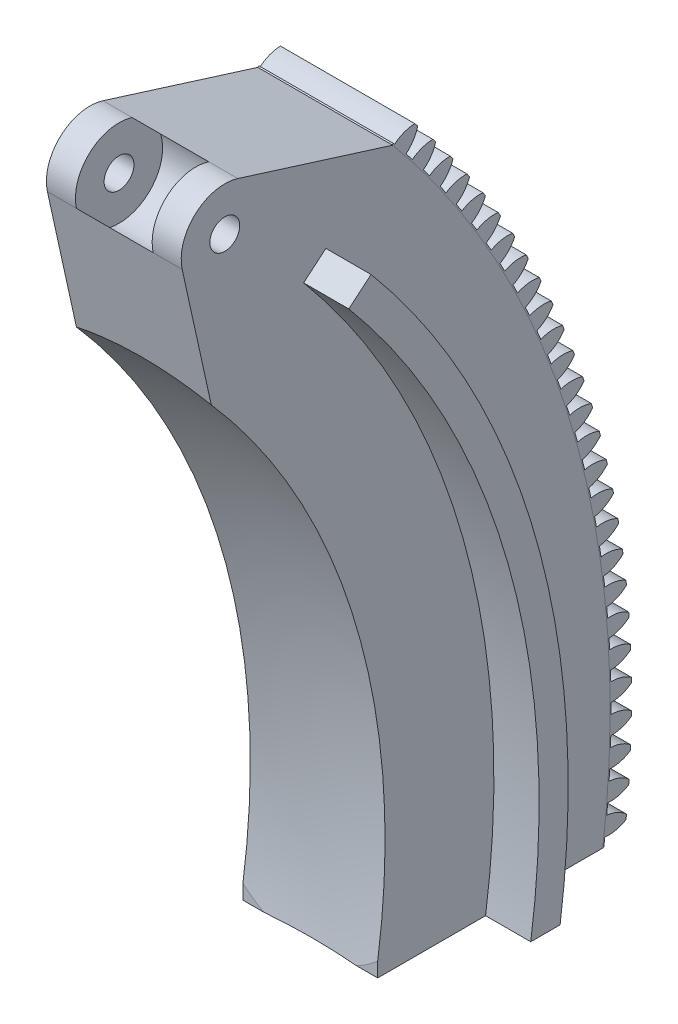
SolidWorks part; units mm, degrees
material "ABS"
ref_plane "Front Plane" through (0, 0, 0) normal (0, 0, 1) x (1, 0, 0)
ref_plane "Top Plane" through (0, 0, 0) normal (0, 1, 0) x (1, 0, 0)
ref_plane "Right Plane" through (0, 0, 0) normal (1, 0, 0) x (0, 0, -1)
ref_plane "Plane2" through (6.35, 0, 0) normal (1, 0, 0) x (0, 0, -1)
sketch "Sketch1" plane through (0, 0, 0) normal (1, 0, 0) x (0, 0, -1)
  line L0 (-1000, 0) -> (152.4, 0) construction
  line L1 (152.4, 0) -> (152.4, -25.4)
  line L2 (0, 0) -> (116.7452, 97.9608) construction
  line L4 (203.2, 0) -> (49000, 0) construction
  line L7 (152.4, -25.4) -> (203.2, -25.4) construction
  line L8 (203.2, 0) -> (203.2, -25.4) construction
  line L10 (-19.9245, -15.6845) -> (159.6649, 125.6875) construction
  line L61 (160.8976, 124.1056) -> (0, 0) construction
  line L62 (116.7452, 97.9608) -> (109.6694, 130.0821)
  line L64 (152.4, -25.4) -> (201.6062, -25.4)
  line L65 (116.7452, 97.9608) -> (136.2027, 114.2876) construction
  line L66 (136.2027, 114.2876) -> (155.6602, 130.6144) construction
  line L68 (0, 0) -> (35966.99, 34732.9185) construction
  line L69 (159.6736, 125.6943) -> (159.6985, 125.714) construction
  line L70 (0, 0) -> (118.9714, 132.1311) construction
  line L71 (121.82, 141.2202) -> (155.6602, 130.6144)
  arc A2 (152.4, 0) -> (116.7452, 97.9608) centre (0, 0) ccw
  circle A19 centre (0, 0) radius 203.2 construction
  arc A22 (155.6602, 130.6144) -> (203.2, 0) centre (0, 0) cw
  arc A23 (203.2, 0) -> (201.6062, -25.4) centre (0, 0) cw
  arc A24 (109.6694, 130.0821) -> (121.82, 141.2202) centre (118.9714, 132.1311) cw
  point P6 (159.6985, 125.714)
  point P7 (116.7452, 97.9608)
  dimension "D1" = 152.4
  dimension "D2" = 6.35
  dimension "D12" = 406.4
  dimension "D8" = 9.525
  dimension "D3" = 40
  dimension "D4" = 50.8
  dimension "D5" = 25.4
  dimension "D6" = 177.8
  dimension "D7" = 48
  dimension "D13" = 44
sketch "Sketch2" plane through (6.35, 0, 0) normal (1, 0, 0) x (0, 0, -1)
  line L0 (0, 0) -> (165.1, 0) construction
  line L1 (165.1, 0) -> (190.5, 0) construction
  line L2 (0, 0) -> (49240.3877, 8682.4089) construction
  circle A0 centre (165.1, 0) radius 3.2639
  circle A1 centre (190.5, 0) radius 3.2639
  arc A3 (165.1, 0) -> (162.5918, 28.6693) centre (0, 0) ccw construction
  circle A4 centre (162.5918, 28.6693) radius 3.2639
  arc A5 (190.5, 0) -> (187.6059, 33.08) centre (0, 0) ccw construction
  circle A6 centre (187.6059, 33.08) radius 3.2639
  dimension "D3" = 6.5278
  dimension "D4" = 6.5278
  dimension "D6" = 6.5278
  dimension "D7" = 6.5278
  dimension "D1" = 165.1
  dimension "D2" = 25.4
  dimension "D5" = 10
sketch "Sketch11" plane through (6.35, 0, 0) normal (1, 0, 0) x (0, 0, -1)
  line L0 (-785.502, -659.1144) -> (0, 0) construction
  line L2 (-1000, 0) -> (0, 0) construction
  line L4 (155.6602, 130.6144) -> (159.3372, 133.6998)
  line L5 (159.3372, 133.6998) -> (921.7047, 773.4021) construction
  line L6 (208, 0) -> (208, -25.4) construction
  line L7 (208, -25.4) -> (198.9391, -25.4) construction
  line L8 (201.6062, -25.4) -> (206.4433, -25.4)
  line L9 (203.2, 0) -> (208, 0) construction
  arc A0 (-230, 0) -> (-176.1902, -147.8412) centre (0, 0) ccw construction
  arc A1 (-208, 0) -> (-159.3372, -133.6998) centre (0, 0) ccw construction
  arc A2 (-205.6, 0) -> (-157.4987, -132.1571) centre (0, 0) ccw construction
  arc A3 (208, 0) -> (159.3372, 133.6998) centre (0, 0) ccw
  arc A4 (230, 0) -> (176.1902, 147.8412) centre (0, 0) ccw construction
  arc A5 (-205.6, 0) -> (-157.4987, -132.1571) centre (0, 0) ccw
  arc A6 (155.6602, 130.6144) -> (203.2, 0) centre (0, 0) cw
  arc A7 (208, 0) -> (206.4433, -25.4) centre (0, 0) cw
  arc A8 (203.2, 0) -> (201.6062, -25.4) centre (0, 0) cw
  dimension "D1" = 460
  dimension "D2" = 416
  dimension "D4" = 203.2
  dimension "D3" = 2.4
  dimension "D6" = 25.4
extrude "Boss-Extrude2" add sketch "Sketch11" against normal blind 6.35 contours A3 L4 region at (6.35, 130.8741, -158.5753)
sketch "Sketch12" plane through (6.35, 0, 0) normal (1, 0, 0) x (0, 0, -1)
  line L0 (0, 0) -> (208, 0) construction
  line L2 (205.994, 1.5708) -> (205.994, -1.5708) construction
  line L3 (0, 0) -> (203.4969, 1.1234) construction
  line L4 (201.6783, 0) -> (208.9831, 2.6587) construction
  line L5 (0, 0) -> (208.9757, 3.1872) construction
  line L6 (205.994, 1.5708) -> (205.9461, 4.712) construction
  circle A0 centre (0, 0) radius 206 construction
  arc A1 (206.4433, -25.4) -> (159.3372, 133.6998) centre (0, 0) ccw construction
  circle A2 centre (0, 0) radius 203.5 construction
  arc A3 (203.4969, 1.1234) -> (208.9694, 3.5771) centre (203.4559, 8.5441) ccw
  arc A4 (207.4358, -25.5221) -> (208.9694, -3.5771) centre (0, 0) cw construction
  arc A5 (203.4969, -1.1234) -> (208.9694, -3.5771) centre (203.4559, -8.5441) cw
  arc A6 (207.4358, -25.5221) -> (160.1033, 134.3426) centre (0, 0) ccw
  arc A7 (207.4358, -25.5221) -> (208.9694, 3.5771) centre (0, 0) ccw construction
  arc A8 (203.4969, 1.1234) -> (203.4969, -1.1234) centre (0, 0) cw
  arc A9 (206.4433, -25.4) -> (159.3372, 133.6998) centre (0, 0) ccw construction
  arc A10 (208.9694, 3.5771) -> (208.9694, -3.5771) centre (0, 0) cw
  dimension "D1" = 412
  dimension "D3" = 20
  dimension "D4" = 0.874
  dimension "D5" = 4.5
  dimension "D2" = 1
extrude "Boss-Extrude3" add sketch "Sketch1" along normal blind 29.464
extrude "Cut-Extrude4" cut sketch "Sketch12" against normal blind 6.35
pattern_circular "CirPattern3" count 206 every 1.748 about axis through (0, 0, 0) along (1, 0, 0) of "Cut-Extrude4"
sketch "Sketch15" plane through (6.35, 0, 0) normal (1, 0, 0) x (0, 0, -1)
  line L0 (0, 0) -> (118.9714, 132.1311) construction
  line L2 (0, 0) -> (102.4673, 0) construction
  circle A0 centre (118.9714, 132.1311) radius 3.2639
  dimension "D3" = 6.5278
  dimension "D1" = 177.8
  dimension "D2" = 48
extrude "Cut-Extrude7" cut sketch "Sketch15" against normal through all both and the other way through all
sketch "Sketch21" plane through (0, 0, 0) normal (0, 1, 0) x (1, 0, 0)
  line L0 (0, 0) -> (-11.1125, 0) construction
  line L1 (12.7, 0) -> (12.7, 152.4) construction
  line L2 (0, 0) -> (12.7, 0) construction
  line L3 (-11.1125, 0) -> (-11.1125, 38.1) construction
  line L4 (-11.1125, 38.1) -> (-127.8666, 38.1) construction
  line L5 (-11.1125, 38.1) -> (105.6416, 38.1) construction
  line L6 (107.5153, 38.1) -> (-49892.4847, 38.1) construction
  line L7 (-1000, 0) -> (49000, 0) construction
  line L8 (14.732, 38.1) -> (14.732, 152.4) construction
  line L9 (29.464, 152.4) -> (0, 152.4) construction
  line L10 (-76.1776, 38.1) -> (157.3306, 38.1) construction
  line L11 (29.464, 152.4) -> (0, 152.4) construction
  line L12 (0, 152.4) -> (14.732, 152.4) construction
  line L13 (14.732, 152.4) -> (14.732, 130.0627) construction
  line L15 (-76.1776, 38.1) -> (-102.108, 38.1)
  line L16 (105.6416, 38.1) -> (131.572, 38.1)
  line L17 (-76.1776, 38.1) -> (105.6416, 38.1)
  arc A0 (105.6416, 38.1) -> (-127.8666, 38.1) centre (-11.1125, 38.1) ccw construction
  arc A1 (-76.1776, 38.1) -> (157.3306, 38.1) centre (40.5765, 38.1) cw construction
  arc A2 (-102.108, 38.1) -> (131.572, 38.1) centre (14.732, 38.1) cw
  dimension "D3" = 12.7
  dimension "D5" = 116.84
  dimension "D1" = 11.1125
  dimension "D2" = 152.4
  dimension "D4" = 38.1
revolve "Cut-Revolve7" cut sketch "Sketch21" angle 360 about L7 reverse direction yes
sketch "Sketch22" plane through (6.35, 0, 0) normal (1, 0, 0) x (0, 0, -1)
  line L0 (0, 0) -> (118.9714, 132.1311)
  line L1 (0, 0) -> (177.8, 0)
  dimension "D1" = 177.8
sketch "Sketch23" plane through (0, 0, 0) normal (1, 0, 0) x (0, 0, -1)
  line L0 (0, 0) -> (152.4, 0) construction
  line L1 (0, 0) -> (116.7452, 97.9608) construction
  line L2 (152.4, 0) -> (171.45, 0) construction
  line L3 (116.7452, 97.9608) -> (136.2027, 114.2876) construction
  line L5 (136.2027, 114.2876) -> (141.0671, 118.3693)
  line L7 (175.9764, -25.4) -> (0, 0) construction
  line L8 (182.3899, -25.4) -> (175.9764, -25.4)
  line L9 (152.4, -25.4) -> (201.9086, -25.4) construction
  arc A0 (152.4, 0) -> (116.7452, 97.9608) centre (0, 0) ccw construction
  circle A2 centre (171.45, 0) radius 6.35 construction
  arc A3 (177.8, 0) -> (136.2027, 114.2876) centre (0, 0) ccw
  arc A4 (184.15, 0) -> (141.0671, 118.3693) centre (0, 0) ccw
  circle A5 centre (190.5, 0) radius 6.35 construction
  arc A6 (177.8, 0) -> (175.9764, -25.4) centre (0, 0) cw
  arc A7 (184.15, 0) -> (182.3899, -25.4) centre (0, 0) cw
  dimension "D4" = 6.35
  dimension "D5" = 12.7
  dimension "D6" = 12.7
  dimension "D1" = 152.4
  dimension "D2" = 40
  dimension "D3" = 19.05
extrude "Boss-Extrude4" add sketch "Sketch23" against normal blind 9.8742
ref_plane "Plane3" through (14.732, 0, 0) normal (1, 0, 0) x (0, 0, -1)
mirror "Mirror2" about plane through (14.732, 0, 0) normal (1, 0, 0) of "Boss-Extrude4"
sketch "Sketch27" plane through (6.35, 0, 0) normal (1, 0, 0) x (0, 0, -1)
  line L2 (155.89, 130.8073) -> (155.6602, 130.6144)
  line L3 (201.6062, -25.4) -> (201.9086, -25.4)
  line L4 (155.89, 130.8073) -> (155.6602, 130.6144)
  line L6 (201.6062, -25.4) -> (201.9086, -25.4)
  arc A95 (207.805, 9.0055) -> (207.7585, 10.0204) centre (0, 0) ccw
  arc A111 (203.368, 7.3287) -> (207.805, 9.0055) centre (203.1007, 14.7447) ccw
  arc A112 (203.368, 7.3287) -> (207.805, 9.0055) centre (203.1007, 14.7447) ccw
  arc A113 (207.7585, 10.0204) -> (203.1869, 11.2847) centre (203.5984, 3.8753) ccw
  arc A114 (207.7585, 10.0204) -> (203.1869, 11.2847) centre (203.5984, 3.8753) ccw
  arc A115 (203.1869, 11.2847) -> (203.0499, 13.5273) centre (0, 0) ccw
  arc A116 (203.1869, 11.2847) -> (203.0499, 13.5273) centre (0, 0) ccw
  arc A117 (203.0499, 13.5273) -> (207.4337, 15.3385) centre (202.5566, 20.9317) ccw
  arc A118 (203.0499, 13.5273) -> (207.4337, 15.3385) centre (202.5566, 20.9317) ccw
  arc A119 (207.4337, 15.3385) -> (207.3563, 16.3516) centre (0, 0) ccw
  arc A120 (207.4337, 15.3385) -> (207.3563, 16.3516) centre (0, 0) ccw
  arc A121 (207.3563, 16.3516) -> (202.7482, 17.4759) centre (203.3855, 10.0825) ccw
  arc A122 (207.3563, 16.3516) -> (202.7482, 17.4759) centre (203.3855, 10.0825) ccw
  arc A123 (202.7482, 17.4759) -> (202.5429, 19.7132) centre (0, 0) ccw
  arc A124 (202.7482, 17.4759) -> (202.5429, 19.7132) centre (0, 0) ccw
  arc A125 (202.5429, 19.7132) -> (206.8694, 21.6573) centre (201.8241, 27.0991) ccw
  arc A126 (202.5429, 19.7132) -> (206.8694, 21.6573) centre (201.8241, 27.0991) ccw
  arc A127 (206.8694, 21.6573) -> (206.7612, 22.6675) centre (0, 0) ccw
  arc A128 (206.8694, 21.6573) -> (206.7612, 22.6675) centre (0, 0) ccw
  arc A129 (206.7612, 22.6675) -> (202.121, 23.6508) centre (202.9834, 16.2802) ccw
  arc A130 (206.7612, 22.6675) -> (202.121, 23.6508) centre (202.9834, 16.2802) ccw
  arc A131 (202.121, 23.6508) -> (201.8476, 25.8808) centre (0, 0) ccw
  arc A132 (202.121, 23.6508) -> (201.8476, 25.8808) centre (0, 0) ccw
  arc A133 (201.8476, 25.8808) -> (206.1127, 27.956) centre (200.9038, 33.2414) ccw
  arc A134 (201.8476, 25.8808) -> (206.1127, 27.956) centre (200.9038, 33.2414) ccw
  arc A135 (206.1127, 27.956) -> (205.9737, 28.9624) centre (0, 0) ccw
  arc A136 (206.1127, 27.956) -> (205.9737, 28.9624) centre (0, 0) ccw
  arc A137 (205.9737, 28.9624) -> (201.3057, 29.8037) centre (202.3925, 22.4629) ccw
  arc A138 (205.9737, 28.9624) -> (201.3057, 29.8037) centre (202.3925, 22.4629) ccw
  arc A139 (201.3057, 29.8037) -> (200.9644, 32.0244) centre (0, 0) ccw
  arc A140 (201.3057, 29.8037) -> (200.9644, 32.0244) centre (0, 0) ccw
  arc A141 (200.9644, 32.0244) -> (205.1643, 34.2286) centre (199.7966, 39.3527) ccw
  arc A142 (200.9644, 32.0244) -> (205.1643, 34.2286) centre (199.7966, 39.3527) ccw
  arc A143 (205.1643, 34.2286) -> (204.9947, 35.2304) centre (0, 0) ccw
  arc A144 (205.1643, 34.2286) -> (204.9947, 35.2304) centre (0, 0) ccw
  arc A145 (204.9947, 35.2304) -> (200.3032, 35.9289) centre (201.6134, 28.6246) ccw
  arc A146 (204.9947, 35.2304) -> (200.3032, 35.9289) centre (201.6134, 28.6246) ccw
  arc A147 (200.3032, 35.9289) -> (199.8943, 38.1381) centre (0, 0) ccw
  arc A148 (200.3032, 35.9289) -> (199.8943, 38.1381) centre (0, 0) ccw
  arc A149 (199.8943, 38.1381) -> (204.0251, 40.4694) centre (198.5036, 45.4275) ccw
  arc A150 (199.8943, 38.1381) -> (204.0251, 40.4694) centre (198.5036, 45.4275) ccw
  arc A151 (204.0251, 40.4694) -> (203.825, 41.4655) centre (0, 0) ccw
  arc A152 (204.0251, 40.4694) -> (203.825, 41.4655) centre (0, 0) ccw
  arc A153 (203.825, 41.4655) -> (199.1143, 42.0207) centre (200.6467, 34.7598) ccw
  arc A154 (203.825, 41.4655) -> (199.1143, 42.0207) centre (200.6467, 34.7598) ccw
  arc A155 (199.1143, 42.0207) -> (198.6383, 44.2164) centre (0, 0) ccw
  arc A156 (199.1143, 42.0207) -> (198.6383, 44.2164) centre (0, 0) ccw
  arc A157 (198.6383, 44.2164) -> (202.696, 46.6726) centre (197.0259, 51.4599) ccw
  arc A158 (198.6383, 44.2164) -> (202.696, 46.6726) centre (197.0259, 51.4599) ccw
  arc A159 (202.696, 46.6726) -> (202.4656, 47.6621) centre (0, 0) ccw
  arc A160 (202.696, 46.6726) -> (202.4656, 47.6621) centre (0, 0) ccw
  arc A161 (202.4656, 47.6621) -> (197.7402, 48.0734) centre (199.4933, 40.8625) ccw
  arc A162 (202.4656, 47.6621) -> (197.7402, 48.0734) centre (199.4933, 40.8625) ccw
  arc A163 (197.7402, 48.0734) -> (197.1975, 50.2535) centre (0, 0) ccw
  arc A164 (197.7402, 48.0734) -> (197.1975, 50.2535) centre (0, 0) ccw
  arc A165 (197.1975, 50.2535) -> (201.1784, 52.8323) centre (195.3649, 57.4445) ccw
  arc A166 (197.1975, 50.2535) -> (201.1784, 52.8323) centre (195.3649, 57.4445) ccw
  arc A167 (201.1784, 52.8323) -> (200.9179, 53.8144) centre (0, 0) ccw
  arc A168 (201.1784, 52.8323) -> (200.9179, 53.8144) centre (0, 0) ccw
  arc A169 (200.9179, 53.8144) -> (196.1822, 54.0813) centre (198.1544, 46.9273) ccw
  arc A170 (200.9179, 53.8144) -> (196.1822, 54.0813) centre (198.1544, 46.9273) ccw
  arc A171 (196.1822, 54.0813) -> (195.5732, 56.2439) centre (0, 0) ccw
  arc A172 (196.1822, 54.0813) -> (195.5732, 56.2439) centre (0, 0) ccw
  arc A173 (195.5732, 56.2439) -> (199.4736, 58.9429) centre (193.5222, 63.3757) ccw
  arc A174 (195.5732, 56.2439) -> (199.4736, 58.9429) centre (193.5222, 63.3757) ccw
  arc A175 (199.4736, 58.9429) -> (199.1834, 59.9166) centre (0, 0) ccw
  arc A176 (199.4736, 58.9429) -> (199.1834, 59.9166) centre (0, 0) ccw
  arc A177 (199.1834, 59.9166) -> (194.4417, 60.039) centre (196.6311, 52.9484) ccw
  arc A178 (199.1834, 59.9166) -> (194.4417, 60.039) centre (196.6311, 52.9484) ccw
  arc A179 (194.4417, 60.039) -> (193.767, 62.182) centre (0, 0) ccw
  arc A180 (194.4417, 60.039) -> (193.767, 62.182) centre (0, 0) ccw
  arc A181 (193.767, 62.182) -> (197.5833, 64.9987) centre (191.4995, 69.2479) ccw
  arc A182 (201.6062, -25.4) -> (155.6602, 130.6144) centre (0, 0) ccw
  arc A183 (193.767, 62.182) -> (197.5833, 64.9987) centre (191.4995, 69.2479) ccw
  arc A184 (197.5833, 64.9987) -> (197.2635, 65.963) centre (0, 0) ccw
  arc A185 (197.5833, 64.9987) -> (197.2635, 65.963) centre (0, 0) ccw
  arc A186 (197.2635, 65.963) -> (192.5203, 65.9408) centre (194.9249, 58.9203) ccw
  arc A187 (197.2635, 65.963) -> (192.5203, 65.9408) centre (194.9249, 58.9203) ccw
  arc A189 (207.805, 9.0055) -> (207.7585, 10.0204) centre (0, 0) ccw
  arc A276 (201.6062, -25.4) -> (155.6602, 130.6144) centre (0, 0) ccw
  arc A282 (192.5203, 65.9408) -> (191.7806, 68.0622) centre (0, 0) ccw
  arc A283 (192.5203, 65.9408) -> (191.7806, 68.0622) centre (0, 0) ccw
  arc A284 (191.7806, 68.0622) -> (195.5092, 70.994) centre (189.2986, 75.0557) ccw
  arc A285 (191.7806, 68.0622) -> (195.5092, 70.994) centre (189.2986, 75.0557) ccw
  arc A286 (195.5092, 70.994) -> (195.1601, 71.9481) centre (0, 0) ccw
  arc A287 (195.5092, 70.994) -> (195.1601, 71.9481) centre (0, 0) ccw
  arc A288 (195.1601, 71.9481) -> (190.4198, 71.7812) centre (193.0374, 64.8374) ccw
  arc A289 (195.1601, 71.9481) -> (190.4198, 71.7812) centre (193.0374, 64.8374) ccw
  arc A290 (190.4198, 71.7812) -> (189.6157, 73.8791) centre (0, 0) ccw
  arc A291 (190.4198, 71.7812) -> (189.6157, 73.8791) centre (0, 0) ccw
  arc A292 (189.6157, 73.8791) -> (193.2532, 76.9233) centre (186.9217, 80.7937) ccw
  arc A293 (189.6157, 73.8791) -> (193.2532, 76.9233) centre (186.9217, 80.7937) ccw
  arc A294 (193.2532, 76.9233) -> (192.8752, 77.8663) centre (0, 0) ccw
  arc A295 (193.2532, 76.9233) -> (192.8752, 77.8663) centre (0, 0) ccw
  arc A296 (192.8752, 77.8663) -> (188.1422, 77.5549) centre (190.9703, 70.6941) ccw
  arc A297 (192.8752, 77.8663) -> (188.1422, 77.5549) centre (190.9703, 70.6941) ccw
  arc A298 (188.1422, 77.5549) -> (187.2745, 79.6273) centre (0, 0) ccw
  arc A299 (188.1422, 77.5549) -> (187.2745, 79.6273) centre (0, 0) ccw
  arc A300 (187.2745, 79.6273) -> (190.8175, 82.781) centre (184.3708, 86.4565) ccw
  arc A301 (187.2745, 79.6273) -> (190.8175, 82.781) centre (184.3708, 86.4565) ccw
  arc A302 (190.8175, 82.781) -> (190.4109, 83.712) centre (0, 0) ccw
  arc A303 (190.8175, 82.781) -> (190.4109, 83.712) centre (0, 0) ccw
  arc A304 (190.4109, 83.712) -> (185.6896, 83.2565) centre (188.7256, 76.4851) ccw
  arc A305 (190.4109, 83.712) -> (185.6896, 83.2565) centre (188.7256, 76.4851) ccw
  arc A306 (185.6896, 83.2565) -> (184.7591, 85.3014) centre (0, 0) ccw
  arc A307 (185.6896, 83.2565) -> (184.7591, 85.3014) centre (0, 0) ccw
  arc A308 (184.7591, 85.3014) -> (188.2042, 88.5617) centre (181.6485, 92.0389) ccw
  arc A309 (184.7591, 85.3014) -> (188.2042, 88.5617) centre (181.6485, 92.0389) ccw
  arc A310 (188.2042, 88.5617) -> (187.7694, 89.4799) centre (0, 0) ccw
  arc A311 (188.2042, 88.5617) -> (187.7694, 89.4799) centre (0, 0) ccw
  arc A312 (187.7694, 89.4799) -> (183.0642, 88.8806) centre (186.3053, 82.2049) ccw
  arc A313 (187.7694, 89.4799) -> (183.0642, 88.8806) centre (186.3053, 82.2049) ccw
  arc A314 (183.0642, 88.8806) -> (182.0718, 90.8962) centre (0, 0) ccw
  arc A315 (183.0642, 88.8806) -> (182.0718, 90.8962) centre (0, 0) ccw
  arc A316 (182.0718, 90.8962) -> (185.4159, 94.26) centre (178.7571, 97.5357) ccw
  arc A317 (182.0718, 90.8962) -> (185.4159, 94.26) centre (178.7571, 97.5357) ccw
  arc A318 (185.4159, 94.26) -> (184.9533, 95.1645) centre (0, 0) ccw
  arc A319 (185.4159, 94.26) -> (184.9533, 95.1645) centre (0, 0) ccw
  arc A320 (184.9533, 95.1645) -> (180.2685, 94.422) centre (183.7117, 87.8483) ccw
  arc A321 (184.9533, 95.1645) -> (180.2685, 94.422) centre (183.7117, 87.8483) ccw
  arc A322 (180.2685, 94.422) -> (179.2151, 96.4064) centre (0, 0) ccw
  arc A323 (180.2685, 94.422) -> (179.2151, 96.4064) centre (0, 0) ccw
  arc A324 (179.2151, 96.4064) -> (182.4551, 99.8706) centre (175.6995, 102.9417) ccw
  arc A325 (179.2151, 96.4064) -> (182.4551, 99.8706) centre (175.6995, 102.9417) ccw
  arc A326 (182.4551, 99.8706) -> (181.9651, 100.7606) centre (0, 0) ccw
  arc A327 (182.4551, 99.8706) -> (181.9651, 100.7606) centre (0, 0) ccw
  arc A328 (181.9651, 100.7606) -> (177.3052, 99.8756) centre (180.9472, 93.4099) ccw
  arc A329 (181.9651, 100.7606) -> (177.3052, 99.8756) centre (180.9472, 93.4099) ccw
  arc A330 (177.3052, 99.8756) -> (176.1917, 101.827) centre (0, 0) ccw
  arc A331 (177.3052, 99.8756) -> (176.1917, 101.827) centre (0, 0) ccw
  arc A332 (176.1917, 101.827) -> (179.3246, 105.3884) centre (172.4785, 108.252) ccw
  arc A333 (176.1917, 101.827) -> (179.3246, 105.3884) centre (172.4785, 108.252) ccw
  arc A334 (179.3246, 105.3884) -> (178.8076, 106.263) centre (0, 0) ccw
  arc A335 (179.3246, 105.3884) -> (178.8076, 106.263) centre (0, 0) ccw
  arc A336 (178.8076, 106.263) -> (174.1769, 105.2362) centre (178.0144, 98.8847) ccw
  arc A337 (178.8076, 106.263) -> (174.1769, 105.2362) centre (178.0144, 98.8847) ccw
  arc A338 (174.1769, 105.2362) -> (173.0044, 107.1528) centre (0, 0) ccw
  arc A339 (174.1769, 105.2362) -> (173.0044, 107.1528) centre (0, 0) ccw
  arc A340 (173.0044, 107.1528) -> (176.0272, 110.8081) centre (169.097, 113.4616) ccw
  arc A341 (173.0044, 107.1528) -> (176.0272, 110.8081) centre (169.097, 113.4616) ccw
  arc A342 (176.0272, 110.8081) -> (175.4839, 111.6665) centre (0, 0) ccw
  arc A343 (176.0272, 110.8081) -> (175.4839, 111.6665) centre (0, 0) ccw
  arc A344 (175.4839, 111.6665) -> (170.8866, 110.499) centre (174.916, 104.2675) ccw
  arc A345 (175.4839, 111.6665) -> (170.8866, 110.499) centre (174.916, 104.2675) ccw
  arc A346 (170.8866, 110.499) -> (169.6562, 112.3789) centre (0, 0) ccw
  arc A347 (170.8866, 110.499) -> (169.6562, 112.3789) centre (0, 0) ccw
  arc A348 (169.6562, 112.3789) -> (172.5661, 116.1247) centre (165.5582, 118.5656) ccw
  arc A349 (169.6562, 112.3789) -> (172.5661, 116.1247) centre (165.5582, 118.5656) ccw
  arc A350 (172.5661, 116.1247) -> (171.9968, 116.9662) centre (0, 0) ccw
  arc A351 (172.5661, 116.1247) -> (171.9968, 116.9662) centre (0, 0) ccw
  arc A352 (171.9968, 116.9662) -> (167.4373, 115.659) centre (171.6549, 109.5532) ccw
  arc A353 (171.9968, 116.9662) -> (167.4373, 115.659) centre (171.6549, 109.5532) ccw
  arc A354 (167.4373, 115.659) -> (166.1502, 117.5005) centre (0, 0) ccw
  arc A355 (167.4373, 115.659) -> (166.1502, 117.5005) centre (0, 0) ccw
  arc A356 (166.1502, 117.5005) -> (168.9445, 121.3333) centre (161.8654, 123.5593) ccw
  arc A357 (166.1502, 117.5005) -> (168.9445, 121.3333) centre (161.8654, 123.5593) ccw
  arc A358 (168.9445, 121.3333) -> (168.3498, 122.157) centre (0, 0) ccw
  arc A359 (168.9445, 121.3333) -> (168.3498, 122.157) centre (0, 0) ccw
  arc A360 (168.3498, 122.157) -> (163.8323, 120.7114) centre (168.2341, 114.7371) ccw
  arc A361 (168.3498, 122.157) -> (163.8323, 120.7114) centre (168.2341, 114.7371) ccw
  arc A362 (163.8323, 120.7114) -> (162.4896, 122.5128) centre (0, 0) ccw
  arc A363 (163.8323, 120.7114) -> (162.4896, 122.5128) centre (0, 0) ccw
  arc A364 (162.4896, 122.5128) -> (165.1657, 126.429) centre (158.022, 128.4382) ccw
  arc A365 (162.4896, 122.5128) -> (165.1657, 126.429) centre (158.022, 128.4382) ccw
  arc A366 (165.1657, 126.429) -> (164.5462, 127.2342) centre (0, 0) ccw
  arc A367 (165.1657, 126.429) -> (164.5462, 127.2342) centre (0, 0) ccw
  arc A368 (164.5462, 127.2342) -> (160.0748, 125.6515) centre (164.6568, 119.8142) ccw
  arc A369 (164.5462, 127.2342) -> (160.0748, 125.6515) centre (164.6568, 119.8142) ccw
  arc A370 (160.0748, 125.6515) -> (158.6778, 127.4111) centre (0, 0) ccw
  arc A371 (160.0748, 125.6515) -> (158.6778, 127.4111) centre (0, 0) ccw
  arc A372 (158.6778, 127.4111) -> (161.2333, 131.4071) centre (154.0317, 133.1975) ccw
  arc A373 (158.6778, 127.4111) -> (161.2333, 131.4071) centre (154.0317, 133.1975) ccw
  arc A374 (161.2333, 131.4071) -> (160.5895, 132.1931) centre (0, 0) ccw
  arc A375 (161.2333, 131.4071) -> (160.5895, 132.1931) centre (0, 0) ccw
  arc A376 (160.5895, 132.1931) -> (156.1685, 130.4747) centre (160.9264, 124.7799) ccw
  arc A377 (160.5895, 132.1931) -> (156.1685, 130.4747) centre (160.9264, 124.7799) ccw
  arc A378 (156.1685, 130.4747) -> (155.89, 130.8073) centre (0, 0) ccw
  arc A379 (156.1685, 130.4747) -> (155.89, 130.8073) centre (0, 0) ccw
  arc A380 (203.4969, -1.1234) -> (203.4969, 1.1234) centre (0, 0) ccw
  arc A381 (203.4969, -1.1234) -> (203.4969, 1.1234) centre (0, 0) ccw
  arc A382 (203.4969, 1.1234) -> (207.9829, 2.664) centre (203.4559, 8.5441) ccw
  arc A383 (203.4969, 1.1234) -> (207.9829, 2.664) centre (203.4559, 8.5441) ccw
  arc A384 (207.9829, 2.664) -> (207.9675, 3.6799) centre (0, 0) ccw
  arc A385 (207.9829, 2.664) -> (207.9675, 3.6799) centre (0, 0) ccw
  arc A386 (207.9675, 3.6799) -> (203.4365, 5.083) centre (203.6219, -2.3355) ccw
  arc A387 (207.9675, 3.6799) -> (203.4365, 5.083) centre (203.6219, -2.3355) ccw
  arc A388 (203.4365, 5.083) -> (203.368, 7.3287) centre (0, 0) ccw
  arc A389 (203.4365, 5.083) -> (203.368, 7.3287) centre (0, 0) ccw
  arc A390 (201.9086, -25.4) -> (202.121, -23.6508) centre (0, 0) ccw
  arc A391 (201.9086, -25.4) -> (202.121, -23.6508) centre (0, 0) ccw
  arc A392 (202.121, -23.6508) -> (206.7612, -22.6675) centre (202.9834, -16.2802) ccw
  arc A393 (202.121, -23.6508) -> (206.7612, -22.6675) centre (202.9834, -16.2802) ccw
  arc A394 (206.7612, -22.6675) -> (206.8694, -21.6573) centre (0, 0) ccw
  arc A395 (206.7612, -22.6675) -> (206.8694, -21.6573) centre (0, 0) ccw
  arc A396 (206.8694, -21.6573) -> (202.5429, -19.7132) centre (201.8241, -27.0991) ccw
  arc A397 (206.8694, -21.6573) -> (202.5429, -19.7132) centre (201.8241, -27.0991) ccw
  arc A398 (202.5429, -19.7132) -> (202.7482, -17.4759) centre (0, 0) ccw
  arc A399 (202.5429, -19.7132) -> (202.7482, -17.4759) centre (0, 0) ccw
  arc A400 (202.7482, -17.4759) -> (207.3563, -16.3516) centre (203.3855, -10.0825) ccw
  arc A401 (202.7482, -17.4759) -> (207.3563, -16.3516) centre (203.3855, -10.0825) ccw
  arc A402 (207.3563, -16.3516) -> (207.4337, -15.3385) centre (0, 0) ccw
  arc A403 (207.3563, -16.3516) -> (207.4337, -15.3385) centre (0, 0) ccw
  arc A404 (207.4337, -15.3385) -> (203.0499, -13.5273) centre (202.5566, -20.9317) ccw
  arc A405 (207.4337, -15.3385) -> (203.0499, -13.5273) centre (202.5566, -20.9317) ccw
  arc A406 (203.0499, -13.5273) -> (203.1869, -11.2847) centre (0, 0) ccw
  arc A407 (203.0499, -13.5273) -> (203.1869, -11.2847) centre (0, 0) ccw
  arc A408 (203.1869, -11.2847) -> (207.7585, -10.0204) centre (203.5984, -3.8753) ccw
  arc A409 (203.1869, -11.2847) -> (207.7585, -10.0204) centre (203.5984, -3.8753) ccw
  arc A410 (207.7585, -10.0204) -> (207.805, -9.0055) centre (0, 0) ccw
  arc A411 (207.7585, -10.0204) -> (207.805, -9.0055) centre (0, 0) ccw
  arc A412 (207.805, -9.0055) -> (203.368, -7.3287) centre (203.1007, -14.7447) ccw
  arc A413 (207.805, -9.0055) -> (203.368, -7.3287) centre (203.1007, -14.7447) ccw
  arc A414 (203.368, -7.3287) -> (203.4365, -5.083) centre (0, 0) ccw
  arc A415 (203.368, -7.3287) -> (203.4365, -5.083) centre (0, 0) ccw
  arc A416 (203.4365, -5.083) -> (207.9675, -3.6799) centre (203.6219, 2.3355) ccw
  arc A417 (203.4365, -5.083) -> (207.9675, -3.6799) centre (203.6219, 2.3355) ccw
  arc A418 (207.9675, -3.6799) -> (207.9829, -2.664) centre (0, 0) ccw
  arc A419 (207.9675, -3.6799) -> (207.9829, -2.664) centre (0, 0) ccw
  arc A420 (207.9829, -2.664) -> (203.4969, -1.1234) centre (203.4559, -8.5441) ccw
  arc A421 (207.9829, -2.664) -> (203.4969, -1.1234) centre (203.4559, -8.5441) ccw
  dimension "D1" = 0
extrude "Boss-Extrude6" add sketch "Sketch27" along normal blind 23.0187
ref_plane "Plane4" through (6.35, 0, 0) normal (-1, 0, 0) x (0, 0, 1)
sketch "Sketch28" plane through (6.35, 0, 0) normal (1, 0, 0) x (0, 0, -1)
  circle A0 centre (118.9714, 132.1311) radius 9.525
  arc A1 (121.82, 141.2202) -> (109.6694, 130.0821) centre (118.9714, 132.1311) ccw construction
extrude "Cut-Extrude8" cut sketch "Sketch28" along normal blind 16.764
equation "\"Module\"= 2mm"
equation "\"Number of Teeth\"= 206"
equation "\"D1@Sketch12\"=\"Module\" * \"Number of Teeth\""
equation "\"D4@Sketch12\"=180 / \"Number of Teeth\""
equation "\"D2\"= 360 / \"Number of Teeth\""
equation "\"D2@Sketch11\"=( \"Number of Teeth\" + 2) * \"Module\""
equation "\"D2@CirPattern3\"= 360 / \"Number of Teeth\""
equation "\"D5@Sketch12\"= 2.25 * \"Module\""
equation "\"D1@Sketch26\"= \"Module\" * \"Number of Teeth\""
equation "\"D1@CirPattern3\"=\"Number of Teeth\""
